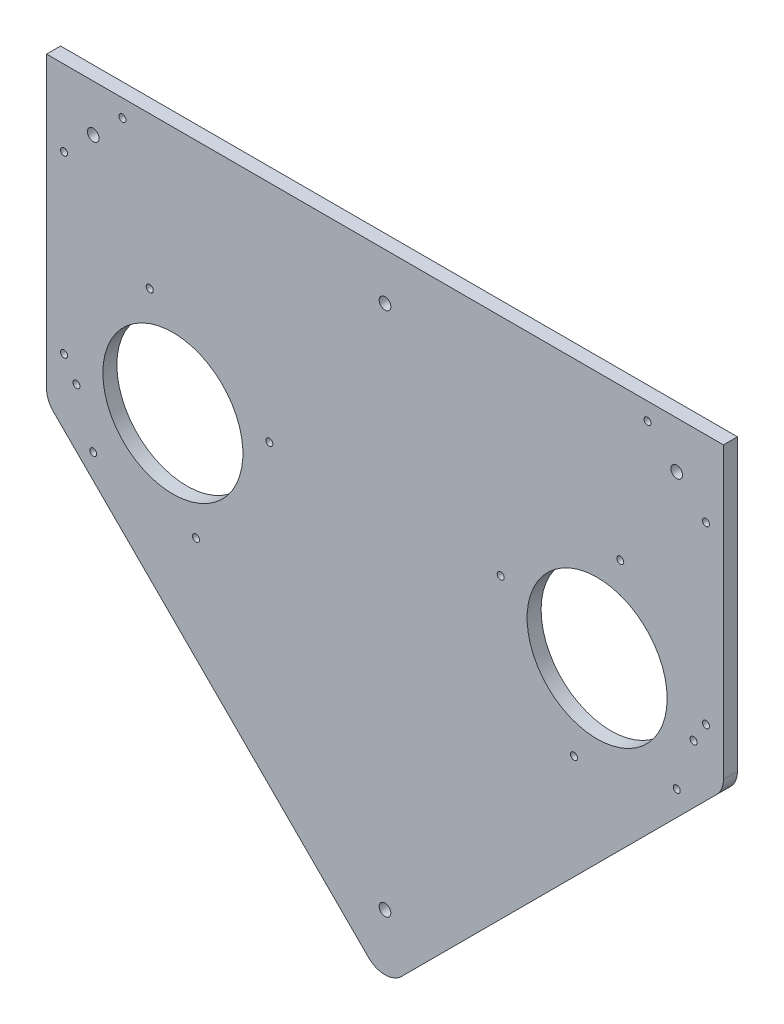
SolidWorks part; units mm, degrees
ref_plane "Front Plane" through (0, 0, 0) normal (0, 0, 1) x (1, 0, 0)
ref_plane "Top Plane" through (0, 0, 0) normal (0, 1, 0) x (1, 0, 0)
ref_plane "Right Plane" through (0, 0, 0) normal (1, 0, 0) x (0, 0, -1)
sketch "Sketch1" plane through (0, 0, 0) normal (0, 0, 1) x (1, 0, 0)
  line L0 (-125, 100) -> (125, 100) construction
  line L1 (-125, 0) -> (125, 0) construction
  line L2 (-137.5158, 87.4842) -> (-125, 100) construction
  line L3 (0, -125) -> (-125, 0) construction
  line L4 (0, -125) -> (-17.7, -125) construction
  line L5 (-125, -17.7) -> (-125, 0) construction
  line L6 (0, -125) -> (0, 100) construction
  line L7 (-145, 120) -> (145, 120)
  line L8 (145, 120) -> (145, -8.2843)
  line L9 (145, -8.2843) -> (0, -153.2843)
  line L10 (0, -153.2843) -> (-145, -8.2843)
  line L11 (-145, -8.2843) -> (-145, 120)
  circle A0 centre (-125, 100) radius 12.7 construction
  circle A1 centre (125, 100) radius 12.7 construction
  circle A4 centre (0, -125) radius 2.5
  circle A5 centre (-137.5158, 87.4842) radius 1.5
  circle A6 centre (-112.4842, 112.5158) radius 1.5
  circle A7 centre (-137.5158, 12.5158) radius 1.5
  circle A8 centre (-125, -17.7) radius 1.5
  circle A10 centre (-125, 0) radius 12.7 construction
  circle A11 centre (125, 0) radius 12.7 construction
  circle A12 centre (-125, 0) radius 17.7 construction
  circle A13 centre (-125, 100) radius 17.7 construction
  circle A14 centre (0, -125) radius 17.7 construction
  circle A16 centre (125, -17.7) radius 1.5
  circle A17 centre (137.5158, 12.5158) radius 1.5
  circle A18 centre (137.5158, 87.4842) radius 1.5
  circle A19 centre (112.4842, 112.5158) radius 1.5
  circle A20 centre (0, 100) radius 2.5
  circle A21 centre (-125, 100) radius 2.5
  circle A22 centre (125, 100) radius 2.5
  point P12 (0, 100)
  point P45 (0, 120)
  dimension "D1" = 25.4
  dimension "D5" = 3
  dimension "D2" = 5
  dimension "D4" = 100
  dimension "D6" = 5
  dimension "D7" = 135
  dimension "D8" = 45
  dimension "D9" = 250
  dimension "D10" = 45
  dimension "D11" = 20
  dimension "D12" = 20
  dimension "D13" = 20
  dimension "D14" = 20
  dimension "D15" = 20
  dimension "D3" = 125
extrude "Boss-Extrude1" add sketch "Sketch1" along normal blind 6
fillet "Fillet1" radius 10 3 edges at (-145, -8.2843, 3) (145, -8.2843, 3) (0, -153.2843, 3)
sketch "Sketch2" plane through (0, 0, 6) normal (0, 0, 1) x (1, 0, 0)
  line L0 (132.2073, 3.8685) -> (49.5554, 23.7093) construction
  line L1 (80.961, -27.5371) -> (100.8017, 55.1149) construction
  line L2 (0, 0) -> (0, 100) construction
  circle A0 centre (90.8813, 13.7889) radius 42.5 construction
  circle A1 centre (49.5554, 23.7093) radius 1.5
  circle A2 centre (100.8017, 55.1149) radius 1.5
  circle A3 centre (132.2073, 3.8685) radius 1.5
  circle A4 centre (80.961, -27.5371) radius 1.5
  circle A5 centre (90.8813, 13.7889) radius 30
  circle A6 centre (-49.5554, 23.7093) radius 1.5
  circle A7 centre (-100.8017, 55.1149) radius 1.5
  circle A8 centre (-80.961, -27.5371) radius 1.5
  circle A9 centre (-132.2073, 3.8685) radius 1.5
  circle A10 centre (-90.8813, 13.7889) radius 42.5 construction
  circle A11 centre (-90.8813, 13.7889) radius 30
  point P6 (90.8813, 13.7889)
  point P27 (-90.8813, 13.7889)
  dimension "D1" = 85
  dimension "D2" = 3
  dimension "D3" = 60
extrude "Cut-Extrude1" cut sketch "Sketch2" against normal blind 10
equation "\"carbon_fiber_tube_diam\"= 1in, 25.4mm"
equation "\"clip_tube_diam\"= 6mm"
equation "\"D1@Sketch1\"=\"carbon_fiber_tube_diam\""
equation "\"middle_tube_len\"= 500mm"
equation "\"horizontal_pipe_spacing\"= 250mm"
equation "\"D9@Sketch1\"=\"horizontal_pipe_spacing\""
